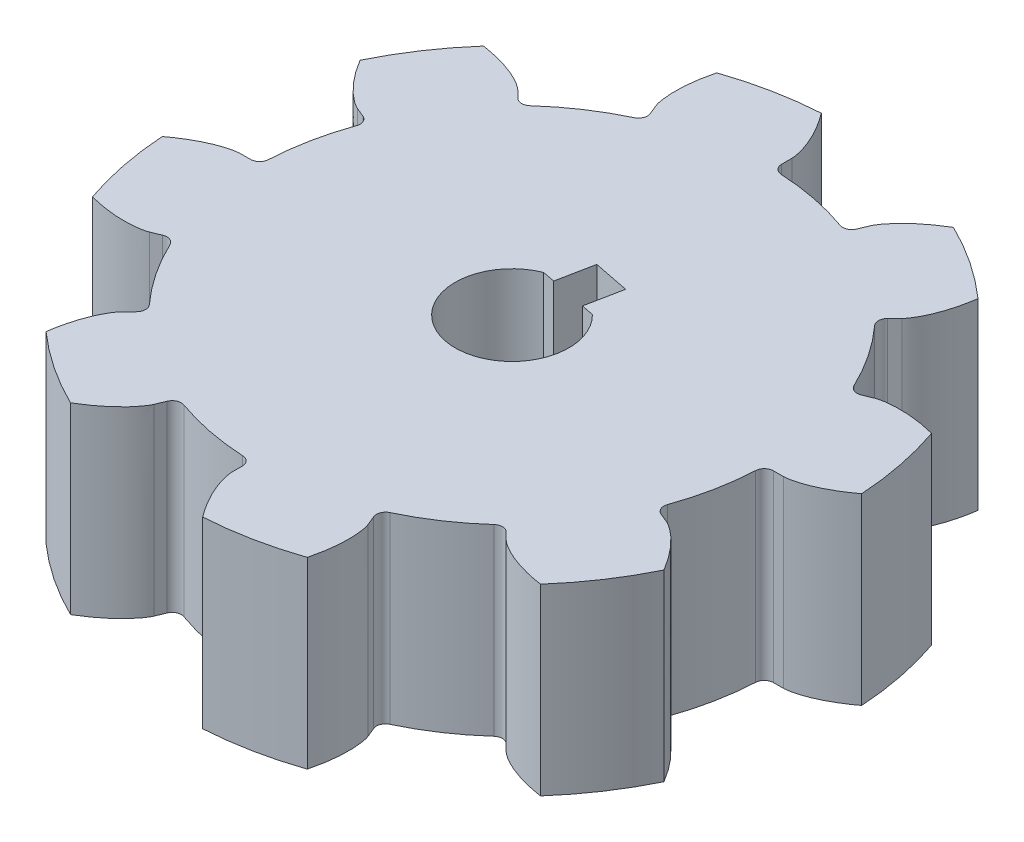
SolidWorks part; units mm, degrees
ref_plane "正面" through (0, 0, 0) normal (0, 0, 1) x (1, 0, 0)
ref_plane "平面" through (0, 0, 0) normal (0, 1, 0) x (1, 0, 0)
ref_plane "右側面" through (0, 0, 0) normal (1, 0, 0) x (0, 0, -1)
sketch "ｽｹｯﾁ1" plane through (0, 0, 0) normal (0, 1, 0) x (1, 0, 0)
  line L0 (0, 0) -> (0, 102.2347) construction
  line L1 (-97.1662, 16) -> (83.1097, 16) construction
  line L2 (-58.4661, -5.2799) -> (63.2436, 39.0188) construction
  circle A0 centre (0, 0) radius 16 construction
  circle A1 centre (0, 0) radius 15.0351 construction
  point P9 (0, 16)
  dimension "D2" = 32
  dimension "D1" = 20
sketch "ｽｹｯﾁ2" plane through (0, 0, 0) normal (0, 1, 0) x (1, 0, 0)
  line L0 (-5.1423, 14.1284) -> (0, 16) construction
  line L1 (-187996.9903, -68409.3086) -> (188001.7678, 68443.0475) construction
  line L2 (-4.3836, 14.3818) -> (0.0857, 15.7441) construction
  line L3 (-3.6125, 14.5946) -> (0.1463, 15.525) construction
  line L4 (-2.8312, 14.7661) -> (0.1861, 15.3446) construction
  line L5 (-2.0419, 14.8958) -> (0.2094, 15.2044) construction
  line L6 (-1.2468, 14.9833) -> (0.2205, 15.1054) construction
  line L7 (-0.4482, 15.0284) -> (0.2239, 15.0484) construction
  line L8 (-5.8864, 13.8349) -> (-0.1148, 16.2906) construction
  line L9 (-6.6139, 13.5022) -> (-0.2626, 16.6133) construction
  line L10 (-7.3226, 13.1314) -> (-0.4471, 16.9655) construction
  line L11 (-8.0106, 12.7233) -> (-0.6717, 17.3439) construction
  line L12 (-8.676, 12.2793) -> (-0.9398, 17.7453) construction
  line L13 (-9.3168, 11.8005) -> (-1.2544, 18.1659) construction
  line L14 (0, 0) -> (-6.4709, 32.5312) construction
  line L15 (0, -200000) -> (0, 200102.2347) construction
  circle A0 centre (0, 0) radius 15.0351 construction
  arc A1 (-5.1423, 14.1284) -> (-4.3836, 14.3818) centre (0, 0) cw
  arc A2 (-4.3836, 14.3818) -> (-3.6125, 14.5946) centre (0, 0) cw
  arc A3 (-3.6125, 14.5946) -> (-2.8312, 14.7661) centre (0, 0) cw
  arc A4 (-2.8312, 14.7661) -> (-2.0419, 14.8958) centre (0, 0) cw
  arc A5 (-2.0419, 14.8958) -> (-1.2468, 14.9833) centre (0, 0) cw
  arc A6 (-1.2468, 14.9833) -> (-0.4482, 15.0284) centre (0, 0) cw
  arc A7 (-5.1423, 14.1284) -> (-5.8864, 13.8349) centre (0, 0) ccw
  arc A8 (-5.8864, 13.8349) -> (-6.6139, 13.5022) centre (0, 0) ccw
  arc A9 (-6.6139, 13.5022) -> (-7.3226, 13.1314) centre (0, 0) ccw
  arc A10 (-7.3226, 13.1314) -> (-8.0106, 12.7233) centre (0, 0) ccw
  arc A11 (-8.0106, 12.7233) -> (-8.676, 12.2793) centre (0, 0) ccw
  arc A12 (-8.676, 12.2793) -> (-9.3168, 11.8005) centre (0, 0) ccw
  arc A13 (-5.1423, 14.1284) -> (0.2241, 15.0334) centre (0, 0) cw
  spline S0 degree 3 poles (-1.2544, 18.1659) (-1.0462, 17.9022) (-0.7654, 17.5086) (-0.4508, 16.9797) (-0.2659, 16.6275) (-0.1177, 16.3048) (-0.0025, 16.0142) (0.0836, 15.7583) (0.1447, 15.5393) (0.1848, 15.3589) (0.2085, 15.2186) (0.2204, 15.1146) (0.224, 15.0574) (0.2241, 15.0334) knots 0 0 0 0 0.287256 0.412688 0.52599 0.627162 0.716204 0.793115 0.857896 0.910546 0.951067 0.979456 1 1 1 1
  spline S1 degree 3 poles (-5.7929, 17.2632) (-5.8843, 16.9399) (-5.9931, 16.4688) (-6.0814, 15.8597) (-6.1175, 15.4636) (-6.1309, 15.1087) (-6.1261, 14.7961) (-6.1077, 14.5268) (-6.0803, 14.301) (-6.0483, 14.119) (-6.0165, 13.9804) (-5.9877, 13.8797) (-5.9692, 13.8255) (-5.9601, 13.8033) knots 0 0 0 0 0.287256 0.412688 0.52599 0.627162 0.716204 0.793115 0.857896 0.910546 0.951067 0.979456 1 1 1 1
  dimension "D1" = 5.4723
  dimension "D3" = 4.6723
  dimension "D4" = 3.8723
  dimension "D5" = 3.0723
  dimension "D6" = 2.2723
  dimension "D7" = 1.4723
  dimension "D8" = 0.6723
  dimension "D9" = 6.2723
  dimension "D10" = 7.0723
  dimension "D11" = 7.8723
  dimension "D12" = 8.6723
  dimension "D13" = 9.4723
  dimension "D14" = 10.2723
  dimension "D15" = 11.25
  dimension "D2" = 0.8
sketch "ｽｹｯﾁ3" plane through (0, 0, 0) normal (0, 1, 0) x (1, 0, 0)
  line L0 (0.2241, 15.0334) -> (0.2241, 13.9982)
  line L1 (0, 0) -> (-6.4709, 32.5312) construction
  line L2 (0, 0) -> (-6.4709, 32.5312) construction
  line L3 (-5.9601, 13.8033) -> (-5.5639, 12.8469)
  arc A0 (0.2241, 13.9982) -> (-5.5639, 12.8469) centre (0, 0) ccw
  arc A1 (-1.1008, 17.9663) -> (-5.8584, 17.02) centre (0, 0) ccw
  spline S0 degree 3 poles (-1.2544, 18.1659) (-1.0462, 17.9022) (-0.7654, 17.5086) (-0.4508, 16.9797) (-0.2659, 16.6275) (-0.1177, 16.3048) (-0.0025, 16.0142) (0.0836, 15.7583) (0.1447, 15.5393) (0.1848, 15.3589) (0.2085, 15.2186) (0.2204, 15.1146) (0.224, 15.0574) (0.2241, 15.0334) knots 0 0 0 0 0.287256 0.412688 0.52599 0.627162 0.716204 0.793115 0.857896 0.910546 0.951067 0.979456 1 1 1 1 construction
  spline S1 degree 3 poles (-5.7929, 17.2632) (-5.8843, 16.9399) (-5.9931, 16.4688) (-6.0814, 15.8597) (-6.1175, 15.4636) (-6.1309, 15.1087) (-6.1261, 14.7961) (-6.1077, 14.5268) (-6.0803, 14.301) (-6.0483, 14.119) (-6.0165, 13.9804) (-5.9877, 13.8797) (-5.9692, 13.8255) (-5.9601, 13.8033) knots 0 0 0 0 0.287256 0.412688 0.52599 0.627162 0.716204 0.793115 0.857896 0.910546 0.951067 0.979456 1 1 1 1 construction
  spline S2 degree 3 poles (-1.1008, 17.9663) (-0.9496, 17.7647) (-0.7225, 17.4365) (-0.4508, 16.9797) (-0.2659, 16.6275) (-0.1177, 16.3048) (-0.0025, 16.0142) (0.0836, 15.7583) (0.1447, 15.5393) (0.1848, 15.3589) (0.2085, 15.2186) (0.2204, 15.1146) (0.224, 15.0574) (0.2241, 15.0334) knots 0 0 0 0 0.232146 0.367277 0.48934 0.598334 0.694261 0.777119 0.846908 0.90363 0.947283 0.977868 1 1 1 1
  spline S3 degree 3 poles (-5.8584, 17.02) (-5.9209, 16.7758) (-6.0052, 16.3857) (-6.0814, 15.8597) (-6.1175, 15.4636) (-6.1309, 15.1087) (-6.1261, 14.7961) (-6.1077, 14.5268) (-6.0803, 14.301) (-6.0483, 14.119) (-6.0165, 13.9804) (-5.9877, 13.8797) (-5.9692, 13.8255) (-5.9601, 13.8033) knots 0 0 0 0 0.232146 0.367277 0.48934 0.598334 0.694261 0.777119 0.846908 0.90363 0.947283 0.977868 1 1 1 1
  point P4 (-5.8584, 17.02)
  point P6 (-1.1008, 17.9663)
  dimension "D1" = 28
  dimension "D2" = 4
sketch "ｽｹｯﾁ4" plane through (0, 0, 0) normal (0, 1, 0) x (1, 0, 0)
  circle A0 centre (0, 0) radius 14
  dimension "D1" = 28
extrude "ﾎﾞｽ - 押し出し1" add sketch "ｽｹｯﾁ4" along normal blind 10
extrude "ﾎﾞｽ - 押し出し2" add sketch "ｽｹｯﾁ3" along normal blind 10
fillet "ﾌｨﾚｯﾄ1" radius 0.5 2 edges at (-5.5639, 5, -12.8469) (0.2241, 5, -13.9982)
pattern_circular "円形ﾊﾟﾀｰﾝ1" count 8 over 360 about axis through (0, 10, 0) along (0, 1, 0) of "ﾎﾞｽ - 押し出し2", "ﾌｨﾚｯﾄ1"
sketch "ｽｹｯﾁ5" plane through (0, 10, 0) normal (0, 1, 0) x (1, 0, 0)
  line L0 (2.6929, 13.5382) -> (-9751.8232, -49025.7258) construction
  line L7 (-1.1485, 2.8794) -> (-0.4736, 2.7451)
  line L8 (-0.4736, 2.7451) -> (-0.0834, 4.7067)
  line L13 (-0.0834, 4.7067) -> (1.8782, 4.3165)
  line L14 (1.8782, 4.3165) -> (1.488, 2.355)
  line L15 (1.488, 2.355) -> (2.163, 2.2207)
  arc A0 (-1.1485, 2.8794) -> (2.163, 2.2207) centre (0, 0) ccw
  arc A1 (4.705, 13.1857) -> (0.6991, 13.9825) centre (0, 0) ccw construction
  arc A2 (-4.705, -13.1857) -> (-0.6991, -13.9825) centre (0, 0) ccw construction
  point P5 (0.8974, 4.5116)
  point P13 (2.7313, 13.731)
  point P19 (-2.7313, -13.731)
  dimension "D1" = 6.2
  dimension "D2" = 2.6
  dimension "D3" = 2
  dimension "D4" = 2
extrude "ｶｯﾄ - 押し出し1" cut sketch "ｽｹｯﾁ5" against normal through all
equation "\"D3@ｽｹｯﾁ2\"=\"D1@ｽｹｯﾁ2\"-\"D2@ｽｹｯﾁ2\""
equation "\"D4@ｽｹｯﾁ2\"=\"D3@ｽｹｯﾁ2\"-\"D2@ｽｹｯﾁ2\""
equation "\"D5@ｽｹｯﾁ2\"=\"D4@ｽｹｯﾁ2\"-\"D2@ｽｹｯﾁ2\""
equation "\"D6@ｽｹｯﾁ2\"=\"D5@ｽｹｯﾁ2\"-\"D2@ｽｹｯﾁ2\""
equation "\"D7@ｽｹｯﾁ2\"=\"D6@ｽｹｯﾁ2\"-\"D2@ｽｹｯﾁ2\""
equation "\"D8@ｽｹｯﾁ2\"=\"D7@ｽｹｯﾁ2\"-\"D2@ｽｹｯﾁ2\""
equation "\"D9@ｽｹｯﾁ2\"=\"D1@ｽｹｯﾁ2\"+\"D2@ｽｹｯﾁ2\""
equation "\"D10@ｽｹｯﾁ2\"=\"D9@ｽｹｯﾁ2\"+\"D2@ｽｹｯﾁ2\""
equation "\"D11@ｽｹｯﾁ2\"=\"D10@ｽｹｯﾁ2\"+\"D2@ｽｹｯﾁ2\""
equation "\"D12@ｽｹｯﾁ2\"=\"D11@ｽｹｯﾁ2\"+\"D2@ｽｹｯﾁ2\""
equation "\"D13@ｽｹｯﾁ2\"=\"D12@ｽｹｯﾁ2\"+\"D2@ｽｹｯﾁ2\""
equation "\"D14@ｽｹｯﾁ2\"=\"D13@ｽｹｯﾁ2\"+\"D2@ｽｹｯﾁ2\""
equation "\"D15@ｽｹｯﾁ2\"=90/8"
